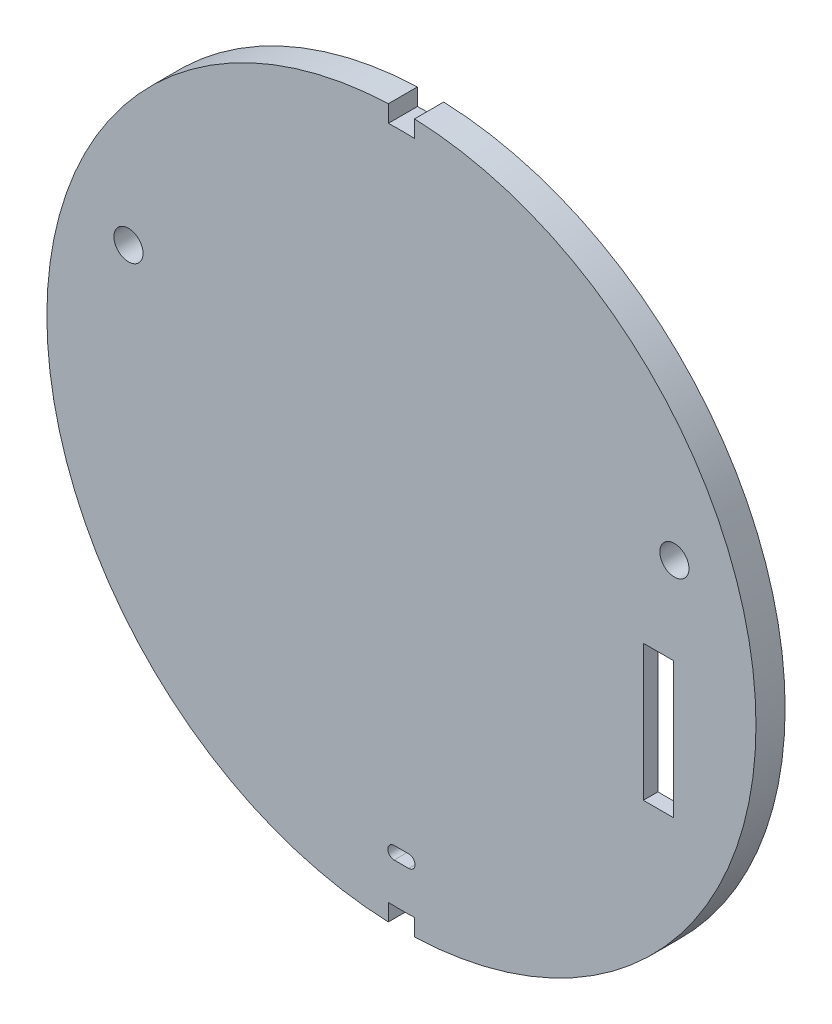
SolidWorks part; units mm, degrees
material "PMMA"
ref_plane "Front Plane" through (0, 0, 0) normal (0, 0, 1) x (1, 0, 0)
ref_plane "Top Plane" through (0, 0, 0) normal (0, 1, 0) x (1, 0, 0)
ref_plane "Right Plane" through (0, 0, 0) normal (1, 0, 0) x (0, 0, -1)
sketch "Sketch1" plane through (0, 0, 0) normal (0, 0, 1) x (1, 0, 0)
  line L0 (0, 45.9969) -> (0, -49.8146) construction
  line L1 (-28, 4.5) -> (28, 4.5)
  line L2 (28, 4.5) -> (28, -17)
  line L3 (28, -17) -> (21.5, -23.5)
  line L4 (21.5, -23.5) -> (-21.5, -23.5)
  line L5 (-21.5, -23.5) -> (-28, -17)
  line L6 (-28, -17) -> (-28, 4.5)
  line L7 (-1.35, 36.475) -> (-1.35, 34.7238)
  line L8 (28, 1.5) -> (24.9, 1.5)
  line L9 (1.35, 34.7238) -> (1.35, 36.475)
  line L10 (24.9, 1.5) -> (24.9, -12.5)
  line L11 (24.9, -12.5) -> (28, -12.5)
  line L12 (28.1, 10.5) -> (-28.1, 10.5) construction
  line L13 (0, 0) -> (16.3469, 0) construction
  line L14 (23.5, -21.5) -> (-23.5, -21.5) construction
  line L15 (23.5, -21.5) -> (23.5, 25.5) construction
  line L16 (23.5, 25.5) -> (-23.5, 25.5) construction
  line L17 (-23.5, -21.5) -> (-23.5, 25.5) construction
  line L18 (23.5, -21.5) -> (-23.5, 25.5) construction
  line L19 (23.5, 25.5) -> (-23.5, -21.5) construction
  line L20 (1.35, -34.7238) -> (1.35, -36.475)
  line L21 (-1.35, -36.475) -> (-1.35, -34.7238)
  line L22 (-0.75, -30) -> (0.75, -30) construction
  line L23 (-0.75, -29.35) -> (0.75, -29.35)
  line L24 (-0.75, -30.65) -> (0.75, -30.65)
  arc A0 (-1.35, 36.475) -> (-1.35, -36.475) centre (0, 0) ccw
  arc A1 (-1.35, 34.7238) -> (1.35, 34.7238) centre (0, 0) cw
  circle A2 centre (28.1, 10.5) radius 1.5
  circle A3 centre (-28.1, 10.5) radius 1.5
  arc A5 (-1.35, -34.7238) -> (1.35, -34.7238) centre (0, 0) ccw
  arc A6 (1.35, -36.475) -> (1.35, 36.475) centre (0, 0) ccw
  arc A7 (-0.75, -29.35) -> (-0.75, -30.65) centre (-0.75, -30) ccw
  arc A8 (0.75, -30.65) -> (0.75, -29.35) centre (0.75, -30) ccw
  point P22 (0, 2)
  point P35 (0, -30)
  point P41 (0.6176, -30)
  point P42 (0, 0)
  point P43 (0.7579, -30)
  dimension "D1" = 73
  dimension "D9" = 34.75
  dimension "D10" = 3
  dimension "D13" = 3
  dimension "D14" = 1.5
  dimension "D18" = 30
  dimension "D20" = 56.2
  dimension "D2" = 56
  dimension "D3" = 21.5
  dimension "D4" = 135
  dimension "D5" = 28
  dimension "D6" = 135
  dimension "D7" = 4.5
  dimension "D8" = 2.7
  dimension "D11" = 17
  dimension "D12" = 3.1
  dimension "D15" = 47
  dimension "D16" = 47
  dimension "D17" = 15
  dimension "D21" = 10.5
  dimension "D22" = 1.3
extrude "Boss-Extrude3" add sketch "Sketch1" against normal blind 3 contours A1 L0 L1 L2 L3 L4 A0 L9 | L0 A1 L7 A0 L4 L5 L6 L1 region at (0, 5.2965, 0)
extrude "Boss-Extrude4" add sketch "Sketch1<9>" against normal blind 1.5 contours L1 L0 L4 L3 L2 L11 L10 L8 | L0 L1 L6 L5 L4 region at (-0.7744, -9.2798, 0)
sketch "Sketch1<9>" plane through (0, 0, 0) normal (0, 0, 1) x (1, 0, 0) same geometry as "Sketch1"
